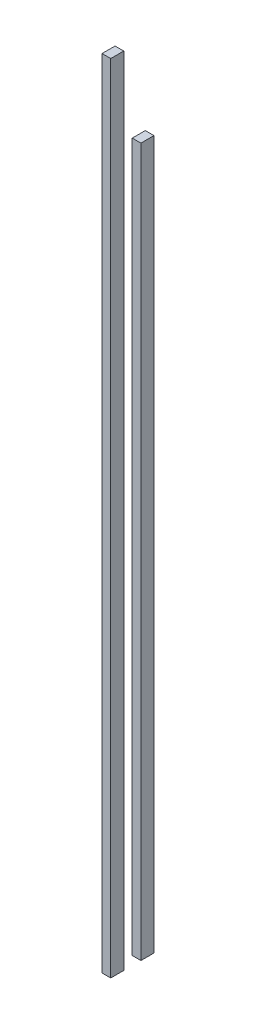
SolidWorks part; units mm, degrees
ref_plane "Front Plane" through (0, 0, 0) normal (0, 0, 1) x (1, 0, 0)
ref_plane "Top Plane" through (0, 0, 0) normal (0, 1, 0) x (1, 0, 0)
ref_plane "Right Plane" through (0, 0, 0) normal (1, 0, 0) x (0, 0, -1)
body saved out of another part "Stock-HoldingPinMP_Diego-1" rebuild error yes
fillet "Fillet1" radius 3 rebuild error yes
sketch "Sketch1" plane through (-3.1, 0, 0) normal (-1, 0, 0) x (0, 0, 1)
  line L0 (2.5275, 62) -> (2.5275, -48)
  line L2 (-1.6468, 49.7863) -> (-1.6468, -48)
  line L3 (6.0522, -48) -> (1.2, -48) construction
  line L4 (2.5275, 62) -> (2.5275, 62.1)
  line L5 (-1.6468, 49.7863) -> (-1.6468, 49.8863)
  dimension "D1" = 0.1
  dimension "D2" = 0.1
  dimension "D3" = 12.2137
extrude "Extrude-Thin1" add sketch "Sketch1" along normal blind 1.2 thin thin type mid plane wall 1.8
mirror "Mirror1" about plane through (0, 0, 0) normal (1, 0, 0) rebuild error yes
sketch "Sketch2" plane through (-3.1, 0, 0) normal (-1, 0, 0) x (0, 0, 1)
  line L1 (-5.2846, 76.6721) -> (-4.9382, 75.8994)
  line L8 (-6.8, 56.2846) -> (-7.6757, 58.4107)
  line L9 (-7.6757, 58.4107) -> (-6.5041, 75.8316)
  line L10 (-6.5041, 75.8316) -> (-11.3855, 74.8554)
  line L11 (-11.3855, 74.8554) -> (-12.3394, 58.7243)
  line L12 (-12.3394, 58.7243) -> (-6.8, 36.7375)
  line L13 (-6.8, 36.7375) -> (-1.8862, 35.8263)
  line L14 (-1.8862, 35.8263) -> (-1.8862, 55.994)
  line L15 (-1.8862, 55.994) -> (-6.8, 56.2846)
  line L17 (-7.706, 59.0581) -> (-4.9382, 75.8994)
  line L21 (-6.8, 36.7375) -> (-1.8862, 35.8263)
  line L22 (-1.8862, 35.8263) -> (-1.8862, 55.994)
  line L23 (-1.8862, 55.994) -> (-7, 59)
  line L34 (-7.3237, 61.3841) -> (-7.8328, 58.2864) construction
  line L44 (-7, 59) -> (-7, 58.8687)
  spline S0 degree 3 poles (-5.2846, 76.6721) (-16.1972, 52.5759) (-6.7103, 43.198) (-6.8, 36.7375) knots 0 0 0 0 1 1 1 1
  spline S1 degree 3 poles (-7, 59) (-6.979, 56.9478) (-7.9308, 57.6898) (-7.706, 59.0581) knots 0 0 0 0 1 1 1 1
  dimension "D1" = 0
extrude "Boss-Extrude1" add sketch "Sketch2" against normal up to surface (6.2 mm away) contours S1 L17 L1 S0 L21 L22 L23 rebuild error yes
fillet "Fillet3" radius 1.5 rebuild error yes
sketch "Sketch4" plane through (0, 62, 0) normal (0, 1, 0) x (1, 0, 0)
  line L0 (3.1, 6.2761) -> (3.5429, 7.1727)
  line L1 (-3.1, 6.2761) -> (-3.5429, 7.1727)
  arc A0 (3.1, 6.2761) -> (0, 7) centre (0, 0) ccw construction
  arc A1 (0, 7) -> (-3.1, 6.2761) centre (0, 0) ccw construction
  arc A2 (3.1, 6.2761) -> (0, 7) centre (0, 0) ccw
  arc A3 (0, 7) -> (-3.1, 6.2761) centre (0, 0) ccw
  arc A4 (3.5429, 7.1727) -> (0, 8) centre (0, 0) ccw
  arc A5 (0, 8) -> (-3.5429, 7.1727) centre (0, 0) ccw
  dimension "D1" = 1
sketch "Sketch5" plane through (0, 40.7906, 23.9777) normal (0, 0.8621, 0.5068) x (1, 0, 0)
  line L2 (-3.1, 35.9333) -> (-3.1, 35.0936)
  line L3 (0, 35.9333) -> (-3.1, 35.9333)
  line L4 (-3.1, 35.9333) -> (-3.1, 35.0936)
  line L5 (0, 35.9333) -> (-3.1, 35.9333)
  ellipse E1 centre (0, 27.8134) end of major axis (0, 35.9333) minor radius 7 (0, 35.9333) -> (-3.1, 35.0936) ccw
  ellipse E2 centre (0, 27.8134) end of major axis (0, 35.9333) minor radius 7 (0, 35.9333) -> (-3.1, 35.0936) ccw
  dimension "D1" = 0
sketch "Sketch6" plane through (0, 0, 0) normal (1, 0, 0) x (0, 0, -1)
  line L4 (7.4341, 60.7122) -> (6.5473, 59.2502)
  line L5 (5.5509, 72.171) -> (7.706, 59.0581) construction
  line L6 (7.4341, 60.7122) -> (7.6488, 59.4057)
  spline S2 degree 3 poles (7.6488, 59.4057) (8.0513, 57.7548) (6.7131, 56.7406) (6.5473, 59.2502) knots 0 0 0 0 1 1 1 1
ref_axis "Axis1" through (0, -47.8517, 0) along (0, 1, 0)
revolve "Cut-Revolve1" cut sketch "Sketch6" angle 60 mid plane about axis through (0, -47.8517, 0) along (0, 1, 0) rebuild error yes
sketch "Sketch7" plane through (0, -48, 0) normal (0, -1, 0) x (1, 0, 0)
  line L0 (0, -6.2851) -> (0, 6.2851) construction
  line L1 (0, -12.3659) -> (-7.8464, -12.3659)
  line L2 (0, -12.3659) -> (0, 9.3879)
  line L3 (0, 9.3879) -> (-7.8464, 9.3879)
  line L4 (-7.8464, -12.3659) -> (-7.8464, 9.3879)
  line L5 (0, -6.6) -> (0, 6.6) construction
fillet "Fillet5" radius 5 rebuild error yes type face fillet
extrude "Cut-Extrude2" cut sketch "Sketch7" against normal through all both and the other way through all rebuild error yes
mirror "Mirror2" about plane through (0, 0, 0) normal (1, 0, 0) rebuild error yes
sketch "Sketch8" plane through (0, 0, 0) normal (1, 0, 0) x (0, 0, -1)
  line L0 (6.087, -38.7504) -> (2.5468, -39.3746) construction
  line L1 (6.087, -38.7504) -> (2.5468, -39.3746)
  line L2 (-1, -40.8391) -> (-1, -47.8) construction
  line L3 (0.7468, -39.692) -> (-0.1736, -39.8543) construction
  line L4 (-1, -40.8391) -> (-1, -47.8)
  line L5 (0.7468, -39.692) -> (-0.1736, -39.8543)
  line L6 (-1, -47.8) -> (-1, -48.7504)
  line L7 (-1, -48.7504) -> (6.087, -48.7504)
  line L8 (6.087, -48.7504) -> (6.087, -38.7504)
  line L9 (0.7468, -39.692) -> (2.5468, -39.3746)
  arc A0 (-0.1736, -39.8543) -> (-1, -40.8391) centre (0, -40.8391) ccw construction
  arc A1 (-0.1736, -39.8543) -> (-1, -40.8391) centre (0, -40.8391) ccw
  dimension "D1" = 10
extrude "Cut-Extrude3" cut sketch "Sketch8" against normal mid plane 20 rebuild error yes
